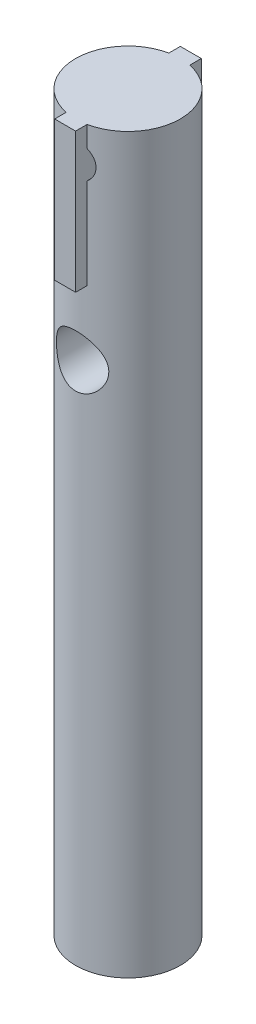
SolidWorks part; units mm, degrees
ref_plane "Front Plane" through (0, 0, 0) normal (0, 0, 1) x (1, 0, 0)
ref_plane "Top Plane" through (0, 0, 0) normal (0, 1, 0) x (1, 0, 0)
ref_plane "Right Plane" through (0, 0, 0) normal (1, 0, 0) x (0, 0, -1)
sketch "Sketch1" plane through (0, 0, 0) normal (0, 1, 0) x (1, 0, 0)
  circle A0 centre (0, 0) radius 7.5
  dimension "D1" = 15
extrude "Boss-Extrude1" add sketch "Sketch1" along normal blind 105
sketch "Sketch2" plane through (0, 0, 0) normal (0, 0, 1) x (1, 0, 0)
  line L0 (0, 105) -> (0, 75)
  line L1 (7.5, 105) -> (-7.5, 105) construction
  circle A0 centre (0, 75) radius 3.75
  dimension "D2" = 7.5
  dimension "D1" = 30
extrude "Cut-Extrude1" cut sketch "Sketch2" against normal through all and the other way through all contours A0 region at (-2.5767, 72.4233, 0)
sketch "Sketch3" plane through (0, 0, 0) normal (0, 0, 1) x (1, 0, 0)
  circle A0 centre (0, 100) radius 2.5
  circle A1 centre (0, 75) radius 3.75 construction
  dimension "D2" = 5
  dimension "D1" = 25
extrude "Cut-Extrude2" cut sketch "Sketch3" against normal blind 10 and the other way blind 10
sketch "Sketch4" plane through (0, 105, 0) normal (0, 1, 0) x (1, 0, 0)
  line L1 (-1.5, -9) -> (1.5, -9)
  line L2 (-1.5, -9) -> (-1.5, 9)
  line L3 (-1.5, 9) -> (1.5, 9)
  line L4 (1.5, -9) -> (1.5, 9)
  line L5 (-1.5, -9) -> (1.5, 9) construction
  line L6 (-1.5, 9) -> (1.5, -9) construction
  point P0 (0, 0)
  dimension "D1" = 3
  dimension "D2" = 18
extrude "Boss-Extrude2" add sketch "Sketch4" against normal blind 20
